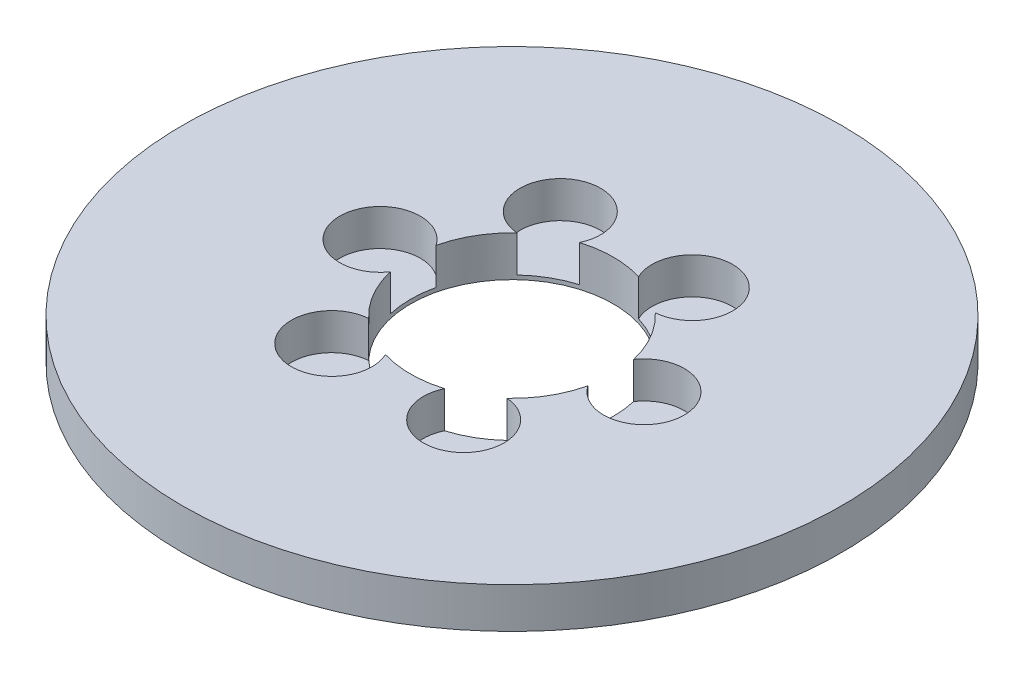
SolidWorks part; units mm, degrees
ref_plane "Front Plane" through (0, 0, 0) normal (0, 0, 1) x (1, 0, 0)
ref_plane "Top Plane" through (0, 0, 0) normal (0, 1, 0) x (1, 0, 0)
ref_plane "Right Plane" through (0, 0, 0) normal (1, 0, 0) x (0, 0, -1)
sketch "Sketch1" plane through (0, 0, 0) normal (0, 1, 0) x (1, 0, 0)
  circle A0 centre (0, 0) radius 32.5
  dimension "FLANGE_OD" = 65
extrude "Boss-Extrude1" add sketch "Sketch1" along normal blind 4
sketch "Sketch2" plane through (0, 0, 0) normal (0, 1, 0) x (1, 0, 0)
  circle A0 centre (0, 0) radius 10
  dimension "BORE_D" = 20
extrude "Cut-Extrude1" cut sketch "Sketch2" along normal through all
sketch "Sketch3" plane through (0, 4, 0) normal (0, 1, 0) x (1, 0, 0)
  circle A0 centre (0, 0) radius 13.0156 construction
  circle A1 centre (-13.0156, 0) radius 3.9778
  dimension "BOLT_D" = 7.9557
  dimension "BOLT_PCD" = 26.0311
extrude "Cut-Extrude2" cut sketch "Sketch3" against normal blind 3.5971
pattern_circular "CirPattern1" count 6 over 360 about axis through (0, 0, 0) along (0, 1, 0) of "Cut-Extrude2"
